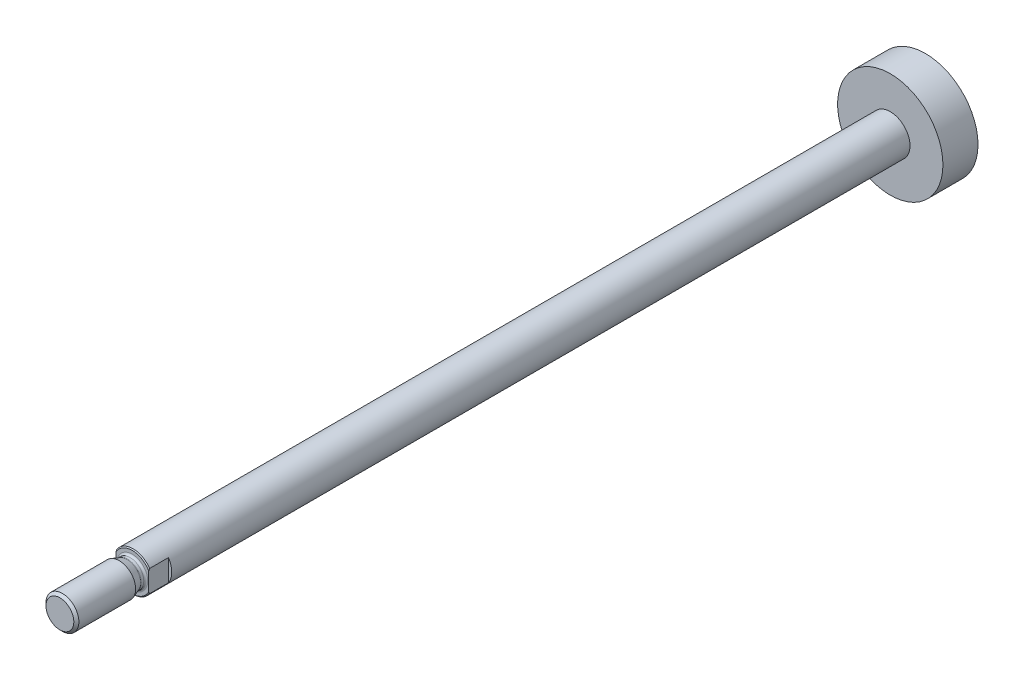
SolidWorks part; units mm, degrees
ref_plane "Front Plane" through (0, 0, 0) normal (0, 0, 1) x (1, 0, 0)
ref_plane "Top Plane" through (0, 0, 0) normal (0, 1, 0) x (1, 0, 0)
ref_plane "Right Plane" through (0, 0, 0) normal (1, 0, 0) x (0, 0, -1)
sketch "Sketch1" plane through (0, 0, 0) normal (1, 0, 0) x (0, 0, -1)
  line L0 (-25.1, 0) -> (-25.1, 5.7172)
  line L1 (-25.1, 5.7172) -> (-24.8172, 6)
  line L2 (-24.8172, 6) -> (205.3333, 6)
  line L3 (205.3333, 6) -> (205.3333, 16)
  line L4 (205.3333, 16) -> (216, 16)
  line L5 (216, 16) -> (216, 0)
  line L6 (216, 0) -> (-25.1, 0)
  line L7 (216, 0) -> (-25.1, 0) construction
revolve "Revolve1" add sketch "Sketch1" angle 360 about L7 reverse direction yes
ref_plane "Plane1" through (0, 0, -205.3333) normal (0, 0, 1) x (1, 0, 0)
sketch "Sketch2" plane through (0, 0, 0) normal (0, 1, 0) x (1, 0, 0)
  line L0 (-10, -39.1) -> (10, -39.1)
  line L1 (10, -39.1) -> (10, -19.1)
  line L2 (10, -19.1) -> (5, -19.1)
  line L3 (5, -19.1) -> (5, -31.1)
  line L4 (5, -31.1) -> (-5, -31.1)
  line L5 (-5, -31.1) -> (-5, -19.1)
  line L6 (-5, -19.1) -> (-10, -19.1)
  line L7 (-10, -19.1) -> (-10, -39.1)
extrude "Cut-Extrude1" cut sketch "Sketch2" along normal blind 10 and the other way blind 10
sketch "Sketch3" plane through (0, 0, 0) normal (1, 0, 0) x (0, 0, -1)
  line L0 (-47.1, 0) -> (-47.1, 4.233)
  line L1 (-47.1, 4.233) -> (-46.333, 5)
  line L2 (-46.333, 5) -> (-29.0727, 5)
  line L3 (-29.0727, 5) -> (-26.6994, 4.1362)
  line L4 (-26.4942, 4.1) -> (-25.7, 4.1)
  line L5 (-25.1, 4.7) -> (-24.5, 4.7)
  line L6 (-24.5, 4.7) -> (-24.5, 0)
  line L7 (-24.5, 0) -> (-47.1, 0)
  line L8 (-24.5, 0) -> (-47.1, 0) construction
  arc A0 (-26.6994, 4.1362) -> (-26.4942, 4.1) centre (-26.4942, 4.7) ccw
  arc A1 (-25.7, 4.1) -> (-25.1, 4.7) centre (-25.7, 4.7) ccw
revolve "Revolve2" add sketch "Sketch3" angle 360 about L8 reverse direction yes
cosmetic thread "Cosmetic Thread1"
ref_plane "Plane2" through (0, 0, -216) normal (0, 0, 1) x (1, 0, 0)
ref_plane "Plane3" through (0, 0, 34.1) normal (0, 0, 1) x (1, 0, 0)
ref_plane "Plane4" through (0, 0, 34.1) normal (0, 0, 1) x (1, 0, 0)
ref_plane "FDT_PIRODACC XY" through (0, 0, 34.1) normal (0, 0, 1) x (1, 0, 0)
ref_plane "FDT_PIRODACC XZ" through (0, 0, 0) normal (0, -1, 0) x (-1, 0, 0)
ref_plane "FDT_PIRODACC YZ" through (0, 0, 0) normal (1, 0, 0) x (0, 0, -1)
ref_axis "FDT_PIRODACC X" through (-80.9, 0, 34.1) along (1, 0, 0)
ref_axis "FDT_PIRODACC Y" through (0, -50, 34.1) along (0, 1, 0)
ref_axis "FDT_PIRODACC Z" through (0, 0, 80.9) along (0, 0, -1)
sketch3d "FDT_PIRODACC"
  point P0 (0, 0, 34.1)
ref_plane "NUT XY" through (0, 0, 34.1) normal (0, 0, -1) x (-1, 0, 0)
ref_plane "NUT XZ" through (0, 0, 0) normal (0, 1, 0) x (1, 0, 0)
ref_plane "NUT YZ" through (0, 0, 0) normal (1, 0, 0) x (0, 0, -1)
ref_axis "NUT X" through (-80.9, 0, 34.1) along (1, 0, 0)
ref_axis "NUT Y" through (0, 50, 34.1) along (0, -1, 0)
ref_axis "NUT Z" through (0, 0, -80.9) along (0, 0, 1)
sketch3d "NUT"
  point P0 (0, 0, 34.1)
ref_plane "P XY" through (0, 0, -216) normal (0, 0, -1) x (-1, 0, 0)
ref_plane "P XZ" through (0, 0, 0) normal (-1, 0, 0) x (0, 0, 1)
ref_plane "P YZ" through (0, 0, 0) normal (0, 1, 0) x (1, 0, 0)
ref_axis "P X" through (0, -50, -216) along (0, 1, 0)
ref_axis "P Y" through (-80.9, 0, -216) along (1, 0, 0)
ref_axis "P Z" through (0, 0, -50) along (0, 0, 1)
sketch3d "P"
  point P0 (0, 0, -216)
other "Freeze***"
